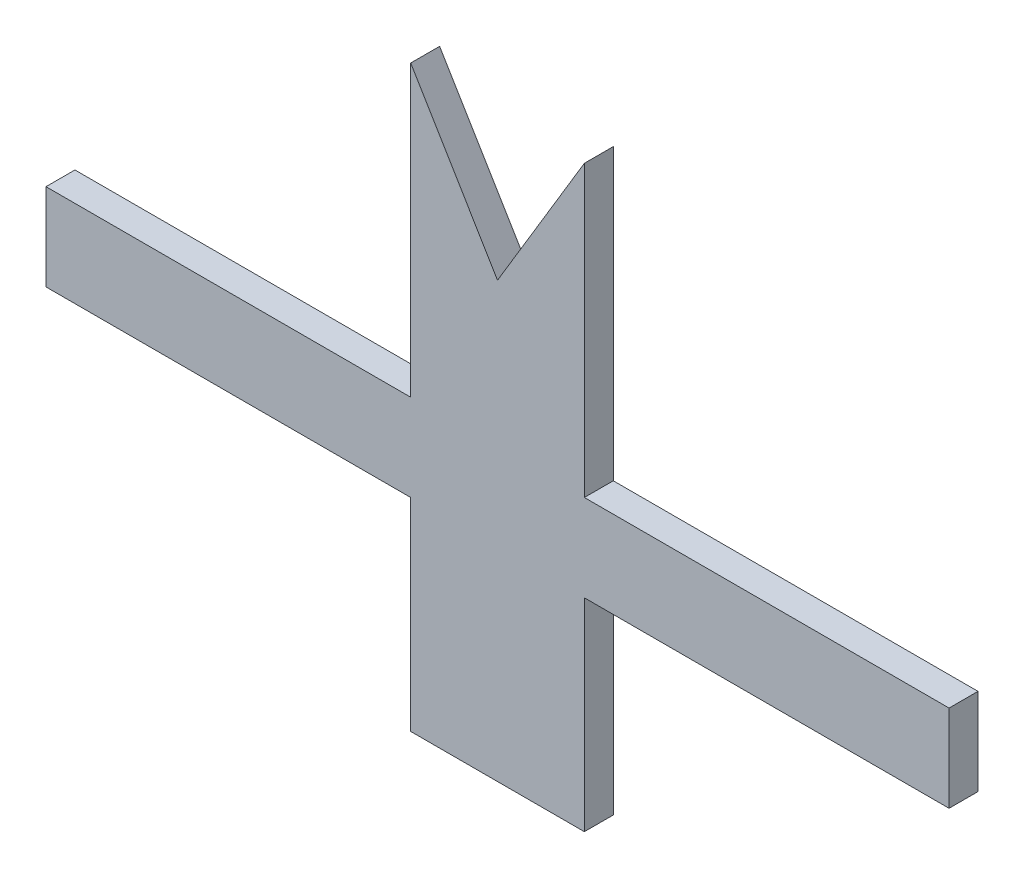
SolidWorks part; units mm, degrees
ref_plane "Front Plane" through (0, 0, 0) normal (0, 0, 1) x (1, 0, 0)
ref_plane "Top Plane" through (0, 0, 0) normal (0, 1, 0) x (1, 0, 0)
ref_plane "Right Plane" through (0, 0, 0) normal (1, 0, 0) x (0, 0, -1)
sketch "Sketch1" plane through (0, 0, 0) normal (0, 0, 1) x (1, 0, 0)
  line L0 (0, 150) -> (60, 150) construction
  line L1 (0, 0) -> (60, 0)
  line L2 (0, 0) -> (0, 200)
  line L3 (0, 200) -> (60, 200) construction
  line L4 (60, 0) -> (60, 200)
  line L5 (0, 200) -> (30, 150)
  line L6 (30, 150) -> (60, 200)
  line L7 (-126, 100) -> (0, 70) construction
  line L8 (0, 100) -> (-126, 100)
  line L9 (0, 100) -> (0, 70)
  line L10 (0, 70) -> (-126, 70)
  line L11 (-126, 100) -> (-126, 70)
  line L12 (0, 100) -> (-126, 70) construction
  line L13 (-63, 85) -> (-126, 85) construction
  line L14 (30, 150) -> (30, 0) construction
  line L15 (60, 100) -> (186, 100)
  line L16 (60, 100) -> (186, 70) construction
  line L17 (186, 100) -> (60, 70) construction
  line L18 (60, 70) -> (186, 70)
  line L19 (123, 85) -> (186, 85) construction
  line L20 (186, 100) -> (186, 70)
  point P7 (30, 150)
  dimension "D1" = 60
  dimension "D2" = 200
  dimension "D3" = 150
  dimension "D4" = 156
  dimension "D5" = 30
  dimension "D6" = 85
extrude "Boss-Extrude1" add sketch "Sketch1" along normal blind 10 contours L8 L11 L10 L2 | L6 L5 L2 L1 L4 | L20 L15 L4 L18 region at (30, 88.0952, 0) region at (-63, 85, 0) region at (123, 85, 0)
